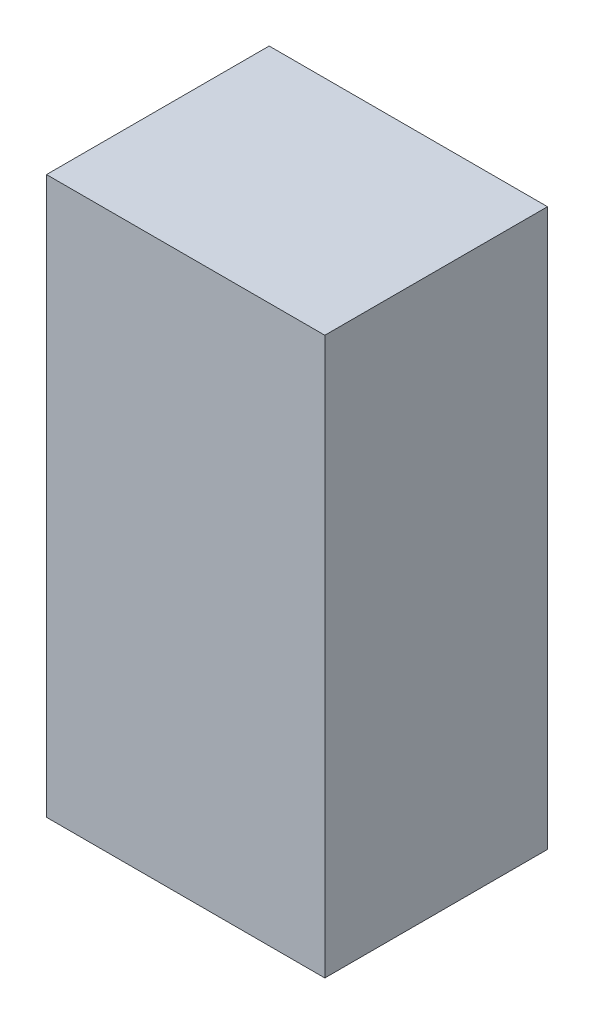
SolidWorks part; units mm, degrees
ref_plane "Front Plane" through (0, 0, 0) normal (0, 0, 1) x (1, 0, 0)
ref_plane "Top Plane" through (0, 0, 0) normal (0, 1, 0) x (1, 0, 0)
ref_plane "Right Plane" through (0, 0, 0) normal (1, 0, 0) x (0, 0, -1)
sketch "Sketch1" plane through (0, 0, 0) normal (0, 1, 0) x (1, 0, 0)
  line L1 (-25, 20) -> (25, 20)
  line L2 (-25, 20) -> (-25, -20)
  line L3 (-25, -20) -> (25, -20)
  line L4 (25, 20) -> (25, -20)
  line L5 (-25, 20) -> (25, -20) construction
  line L6 (-25, -20) -> (25, 20) construction
  point P0 (0, 0)
  dimension "D1" = 50
  dimension "D2" = 40
extrude "Boss-Extrude1" add sketch "Sketch1" along normal blind 100
ref_axis "Axis1" through (0, 105, 0) along (0, -1, 0)
